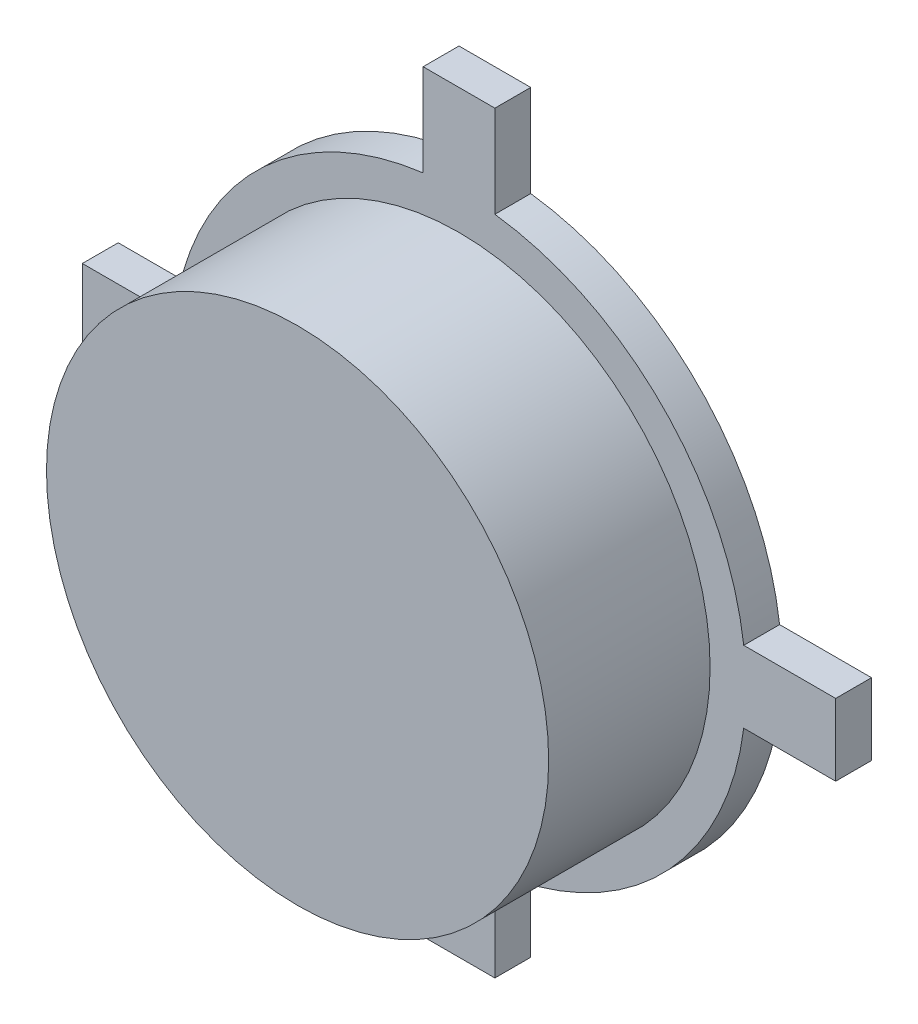
SolidWorks part; units mm, degrees
ref_plane "Front Plane" through (0, 0, 0) normal (0, 0, 1) x (1, 0, 0)
ref_plane "Top Plane" through (0, 0, 0) normal (0, 1, 0) x (1, 0, 0)
ref_plane "Right Plane" through (0, 0, 0) normal (1, 0, 0) x (0, 0, -1)
sketch "Sketch1" plane through (0, 0, 0) normal (0, 0, 1) x (1, 0, 0)
  circle A0 centre (0, 0) radius 7
  circle A1 centre (0, 0) radius 7.5 construction
  dimension "D1" = 0.5
extrude "Boss-Extrude1" add sketch "Sketch1" along normal blind 4.5
sketch "Sketch4" plane through (0, 0, 0) normal (0, 0, -1) x (-1, 0, 0)
  line L110 (10.5, 1) -> (7.9373, 1)
  line L111 (10.5, -1) -> (10.5, 1)
  line L112 (7.9373, -1) -> (10.5, -1)
  line L113 (1, -10.5) -> (1, -7.9373)
  line L114 (-1, -10.5) -> (1, -10.5)
  line L115 (-1, -7.9373) -> (-1, -10.5)
  line L116 (-10.5, -1) -> (-7.9373, -1)
  line L117 (-10.5, 1) -> (-10.5, -1)
  line L118 (-7.9373, 1) -> (-10.5, 1)
  line L119 (-1, 10.5) -> (-1, 7.9373)
  line L120 (1, 7.9373) -> (1, 10.5)
  line L121 (1, 10.5) -> (-1, 10.5)
  line L122 (10.5, 1) -> (7.9373, 1)
  line L123 (10.5, -1) -> (10.5, 1)
  line L124 (7.9373, -1) -> (10.5, -1)
  line L125 (1, -10.5) -> (1, -7.9373)
  line L126 (-1, -10.5) -> (1, -10.5)
  line L127 (-1, -7.9373) -> (-1, -10.5)
  line L128 (-10.5, -1) -> (-7.9373, -1)
  line L129 (-10.5, 1) -> (-10.5, -1)
  line L130 (-7.9373, 1) -> (-10.5, 1)
  line L131 (-1, 10.5) -> (-1, 7.9373)
  line L132 (1, 7.9373) -> (1, 10.5)
  line L133 (1, 10.5) -> (-1, 10.5)
  arc A42 (1, -7.9373) -> (7.9373, -1) centre (0, 0) ccw
  arc A43 (-7.9373, -1) -> (-1, -7.9373) centre (0, 0) ccw
  arc A44 (-1, 7.9373) -> (-7.9373, 1) centre (0, 0) ccw
  arc A45 (7.9373, 1) -> (1, 7.9373) centre (0, 0) ccw
  arc A46 (1, -7.9373) -> (7.9373, -1) centre (0, 0) ccw
  arc A47 (-7.9373, -1) -> (-1, -7.9373) centre (0, 0) ccw
  arc A48 (-1, 7.9373) -> (-7.9373, 1) centre (0, 0) ccw
  arc A49 (7.9373, 1) -> (1, 7.9373) centre (0, 0) ccw
  dimension "D1" = 0.5
extrude "Boss-Extrude3" add sketch "Sketch4" along normal blind 1
